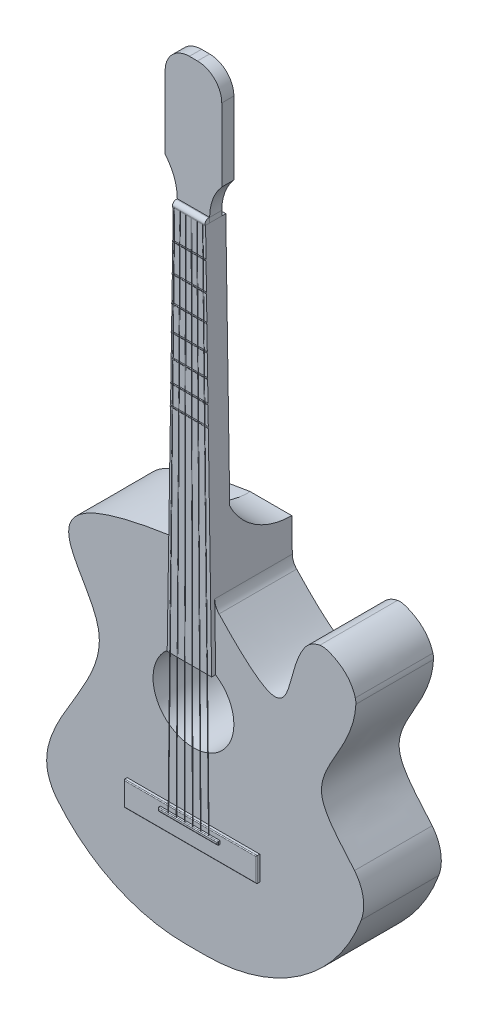
SolidWorks part; units mm, degrees
ref_plane "Front Plane" through (0, 0, 0) normal (0, 0, 1) x (1, 0, 0)
ref_plane "Top Plane" through (0, 0, 0) normal (0, 1, 0) x (1, 0, 0)
ref_plane "Right Plane" through (0, 0, 0) normal (1, 0, 0) x (0, 0, -1)
sketch "Sketch1" plane through (0, 0, 0) normal (0, 0, 1) x (1, 0, 0)
  line L0 (0, 0) -> (40, 0)
  line L2 (0, -480) -> (40, -480)
  line L4 (20, -480) -> (-7.5, -480)
  line L5 (0, 0) -> (-7.5, -480)
  line L7 (40, 0) -> (47.5, -480)
  line L8 (40, -480) -> (47.5, -480)
  dimension "D1" = 40
  dimension "D2" = 480
  dimension "D3" = 27.5
extrude "Boss-Extrude1" add sketch "Sketch1" against normal blind 20 contours L2 L8 L7 L0 L5 L4
sketch "Sketch2" plane through (0, 0, 0) normal (0, 0, 1) x (1, 0, 0)
  line L2 (-7.5, -480) -> (-5.2648, -358.4843)
  line L3 (47.5, -480) -> (-7.5, -480)
  line L4 (10.2196, -786.9686) -> (35.1477, -786.9686)
  line L8 (-5.2648, -358.4843) -> (45.6013, -358.4843)
  line L9 (275.2698, -356.9686) -> (275.2698, -421.9686)
  line L11 (47.5, -480) -> (46.5933, -421.9686)
  line L14 (45.6013, -358.4843) -> (46.3625, -407.203)
  arc A1 (10.2196, -786.9686) -> (-148.7175, -711.4444) centre (10.2196, -581.9686) cw
  arc A2 (35.1477, -786.9686) -> (227.4372, -653.0301) centre (35.1477, -581.9686) ccw
  arc A4 (157.4382, -396.211) -> (176.367, -383.9954) centre (181.9795, -413.4658) cw
  arc A5 (220.8514, -425.0649) -> (220.1344, -418.6037) centre (200.8792, -424.0107) ccw
  arc A6 (227.4372, -653.0301) -> (219.1936, -603.9853) centre (180.5374, -635.698) ccw
  spline S0 degree 2 poles (45.6013, -358.4843) (46.0973, -390.2265) (46.5933, -421.9686) knots 0.023318 0.023318 0.023318 1 1 1
  spline S1 degree 3 poles (-5.2648, -358.4843) (-217.8246, -389.3439) (15.0576, -504.241) (-198.228, -649.3722) (-148.7175, -711.4444) knots 0 0 0 0 0.481381 1 1 1 1
  spline S2 degree 3 poles (219.1936, -603.9853) (202.3906, -583.5033) (147.1519, -529.6114) (218.1524, -476.2006) (220.8514, -425.0649) knots 0.199231 0.199231 0.199231 0.199231 0.323151 0.537685 0.537685 0.537685 0.537685
  spline S3 degree 3 poles (176.367, -383.9954) (180.6636, -383.1772) (200.0573, -388.9291) (215.47, -401.9931) (220.1344, -418.6037) knots 0.180917 0.180917 0.180917 0.180917 0.355528 0.960011 0.960011 0.960011 0.960011
  spline S4 degree 3 poles (157.4382, -396.211) (126.9257, -439.6088) (154.8161, -524.8629) (46.3625, -407.203) knots 0.793266 0.793266 0.793266 0.793266 1 1 1 1
  dimension "D1" = 65
  dimension "D4" = 205
  dimension "D5" = 205
  dimension "D2" = 30
  dimension "D6" = 20
  dimension "D7" = 50
extrude "Boss-Extrude2" add sketch "Sketch2" against normal blind 96 contours A4 S4 S0 L11 L3 L2 S1 A1 L4 A2 A6 S2 A5 S3
fillet "Fillet3" radius 20 1 edges at (46.3625, -407.203, -48)
sketch "Sketch3" plane through (0, 0, 0) normal (0, 0, 1) x (1, 0, 0)
  line L0 (0, 0) -> (40, 0)
sketch "Sketch4" plane through (0, 0, 0) normal (0, 0, 1) x (1, 0, 0)
  line L0 (-7.5, -480) -> (0, 0)
  line L1 (0, 0) -> (40, 0)
  line L2 (40, 0) -> (47.5, -480)
  line L3 (47.5, -480) -> (-7.5, -480)
extrude "Boss-Extrude3" add sketch "Sketch4" along normal blind 5
sketch "Sketch5" plane through (0, 0, 0) normal (0, 0, 1) x (1, 0, 0)
  line L0 (45.6013, -358.4843) -> (-5.2648, -358.4843)
  line L2 (0, 0) -> (-5.6021, -358.5333) construction
  line L3 (-4.8537, -310.6349) -> (44.8537, -310.6349)
  line L4 (40, 0) -> (45.6013, -358.4843) construction
  line L5 (44.8537, -310.6349) -> (45.6013, -358.4843)
  line L6 (-4.8537, -310.6349) -> (-5.6021, -358.5333)
  line L7 (-5.6021, -358.5333) -> (-5.2648, -358.4843)
extrude "Boss-Extrude4" add sketch "Sketch5" against normal blind 96
chamfer "Chamfer1" distance 48 angle 45 1 edges at (20, -310.6349, -96)
sketch "Sketch7" plane through (0, 0, 0) normal (1, 0, 0) x (0, 0, -1)
  line L0 (20, -291.734) -> (20, -310.6349)
  line L1 (20, 0) -> (20, -310.6349) construction
  line L2 (20, -291.734) -> (20, -310.6349)
  line L3 (20, -291.734) -> (20, -310.6349)
  line L4 (96, -379.0809) -> (96, -358.6349)
  line L5 (96, -358.6349) -> (96, -399.527) construction
  line L6 (20, -310.6349) -> (96, -310.6349)
  line L7 (96, -310.6349) -> (96, -358.6349)
  arc A0 (96, -358.6349) -> (20, -310.6349) centre (96, -274.4682) cw
extrude "Cut-Extrude1" cut sketch "Sketch7" along normal mid plane 110 contours A0 L7 L6
sketch "Sketch8" plane through (0, 0, 0) normal (0, 0, 1) x (1, 0, 0)
  line L0 (20, -480) -> (20, -472)
  line L1 (-7.5, -480) -> (47.5, -480) construction
  line L2 (20, -472) -> (20, -572)
  circle A0 centre (20, -522) radius 50
  dimension "D1" = 8
  dimension "D2" = 100
sketch "Sketch9" plane through (0, 0, 0) normal (0, 0, 1) x (1, 0, 0)
  circle A0 centre (20, -522) radius 50
sketch "Sketch28" plane through (0, 0, 0) normal (0, 0, 1) x (1, 0, 0)
  circle A0 centre (20, -522) radius 50
extrude "Cut-Extrude14" cut sketch "Sketch28" against normal blind 80
sketch "Sketch30" plane through (0, 0, 5) normal (0, 0, 1) x (1, 0, 0)
  line L0 (0, -162) -> (-2.5312, -162)
  line L3 (0, -162) -> (40.5938, -162)
  line L8 (39.7524, -36) -> (40.5625, -36)
  line L9 (0, -36) -> (39.7524, -36)
  line L11 (0, -38) -> (39.7524, -38)
  line L13 (47.5, -480) -> (40, 0) construction
  line L14 (40.5625, -36) -> (40.5938, -38)
  line L15 (40.5938, -38) -> (39.7524, -38)
  line L16 (0, -36) -> (-0.5625, -36)
  line L17 (0, 0) -> (-7.5, -480) construction
  line L18 (-0.5625, -36) -> (-0.5937, -38)
  line L19 (-0.5937, -38) -> (0, -38)
  line L20 (0, -71) -> (-1.1094, -71)
  line L21 (0, -71) -> (39.7524, -71)
  line L23 (0, -73) -> (39.7524, -73)
  line L25 (-1.1094, -71) -> (-1.1406, -73)
  line L26 (-1.1406, -73) -> (0, -73)
  line L27 (39.7524, -71) -> (41.1094, -71)
  line L28 (41.1094, -71) -> (41.1406, -73)
  line L29 (41.1406, -73) -> (39.7524, -73)
  line L30 (39.7524, -103) -> (41.6094, -103)
  line L31 (0, -103) -> (39.7524, -103)
  line L33 (0, -105) -> (39.7524, -105)
  line L35 (41.6094, -103) -> (41.6406, -105)
  line L36 (41.6406, -105) -> (39.7524, -105)
  line L37 (0, -103) -> (-1.6094, -103)
  line L38 (-1.6094, -103) -> (-1.6406, -105)
  line L39 (-1.6406, -105) -> (0, -105)
  line L40 (0, -134) -> (-2.0937, -134)
  line L41 (0, -134) -> (40.5938, -134)
  line L43 (0, -136) -> (40.5938, -136)
  line L45 (-2.0937, -134) -> (-2.125, -136)
  line L46 (-2.125, -136) -> (0, -136)
  line L47 (40.5938, -134) -> (42.0938, -134)
  line L48 (42.0938, -134) -> (42.125, -136)
  line L49 (42.125, -136) -> (40.5938, -136)
  line L50 (0, -164) -> (40.5938, -164)
  line L52 (-2.5312, -162) -> (-2.5625, -164)
  line L53 (-2.5625, -164) -> (0, -164)
  line L54 (40.5938, -162) -> (42.5313, -162)
  line L55 (42.5313, -162) -> (42.5625, -164)
  line L56 (42.5625, -164) -> (40.5938, -164)
  line L57 (0, -189) -> (-2.9531, -189)
  line L58 (0, -189) -> (39.7524, -189)
  line L60 (0, -191) -> (39.7524, -191)
  line L62 (-2.9531, -189) -> (-2.9844, -191)
  line L63 (-2.9844, -191) -> (0, -191)
  line L64 (39.7524, -189) -> (42.9531, -189)
  line L65 (42.9531, -189) -> (42.9844, -191)
  line L66 (42.9844, -191) -> (39.7524, -191)
  line L67 (0, -214) -> (-3.3437, -214)
  line L68 (0, -214) -> (40.5938, -214)
  line L70 (0, -216) -> (40.5938, -216)
  line L72 (-3.3437, -214) -> (-3.375, -216)
  line L73 (-3.375, -216) -> (0, -216)
  line L74 (40.5938, -214) -> (43.3438, -214)
  line L75 (43.3438, -214) -> (43.375, -216)
  line L76 (43.375, -216) -> (40.5938, -216)
  dimension "D2" = 35
  dimension "D3" = 32
  dimension "D4" = 31
  dimension "D5" = 28
  dimension "D6" = 27
  dimension "D7" = 25
  dimension "D8" = 2
  dimension "D9" = 2
  dimension "D10" = 2
  dimension "D11" = 2
  dimension "D12" = 2
  dimension "D13" = 2
  dimension "D14" = 2
extrude "Boss-Extrude18" add sketch "Sketch30" along normal blind 0.5
fillet "Fillet31" radius 1 14 edges at (20, -216, 5.5) (20, -214, 5.5) (20, -191, 5.5) (20, -189, 5.5) (20, -164, 5.5) (20, -162, 5.5) (20, -136, 5.5) (20, -134, 5.5) (20, -105, 5.5) (20, -103, 5.5) (20, -73, 5.5) (20, -71, 5.5) (20, -38, 5.5) (20, -36, 5.5)
sketch "Sketch31" plane through (0, 0, 0) normal (0, 0, 1) x (1, 0, 0)
  line L0 (0, 0) -> (0, 6)
  line L1 (40, 0) -> (40, 6)
  line L2 (40, 6) -> (0, 6)
  line L3 (0, 0) -> (40, 0)
  dimension "D1" = 6
sketch "Sketch32" plane through (0, 0, 5) normal (0, 0, 1) x (1, 0, 0)
  line L1 (0, 0) -> (40, 0)
  line L2 (0, 0) -> (0, 6)
  line L3 (0, 6) -> (40, 6)
  line L4 (40, 0) -> (40, 6)
extrude "Boss-Extrude19" add sketch "Sketch32" along normal blind 1 separate body
sketch "Sketch33" plane through (0, 0, 5) normal (0, 0, -1) x (-1, 0, 0)
  line L1 (-40, 0) -> (0, 0)
  line L2 (-40, 0) -> (-40, 6)
  line L3 (-40, 6) -> (0, 6)
  line L4 (0, 0) -> (0, 6)
extrude "Boss-Extrude20" add sketch "Sketch33" along normal blind 5
fillet "Fillet32" radius 5 1 edges at (20, 6, 6)
sketch "Sketch34" plane through (0, 0, 0) normal (0, 0, 1) x (1, 0, 0)
  line L1 (20, -645) -> (-17, -645)
  line L2 (20, -645) -> (-62, -645)
  line L3 (20, -645) -> (102, -645)
  line L4 (-62, -645) -> (-62, -675)
  line L5 (-62, -675) -> (102, -675)
  line L6 (102, -675) -> (102, -645)
  line L8 (20, -651) -> (-17, -651)
  line L9 (-17, -651) -> (-17, -655)
  line L10 (-17, -655) -> (57, -655)
  line L11 (57, -655) -> (57, -651)
  line L12 (57, -651) -> (20, -651)
  dimension "D2" = 37
  dimension "D3" = 82
  dimension "D4" = 82
  dimension "D5" = 30
  dimension "D6" = 6
  dimension "D7" = 4
  dimension "D8" = 74
extrude "Boss-Extrude21" add sketch "Sketch34" along normal blind 4 contours L5 L6 L3 L1 L2 L4 L12 L11 L10 L9 L8
sketch "Sketch35" plane through (0, 0, 4) normal (0, 0, 1) x (1, 0, 0)
  line L1 (-17, -655) -> (57, -655)
  line L2 (-17, -655) -> (-17, -651)
  line L3 (-17, -651) -> (57, -651)
  line L4 (57, -655) -> (57, -651)
extrude "Boss-Extrude22" add sketch "Sketch35" along normal blind 3 separate body
fillet "Fillet33" radius 1 4 edges at (102, -660, 4) (20, -675, 4) (-62, -660, 4) (20, -645, 4)
fillet "Fillet34" radius 1 4 edges at (-17, -653, 7) (57, -653, 7) (20, -655, 7) (20, -651, 7)
sketch "Sketch36" plane through (0, 0, 6) normal (0, 0, 1) x (1, 0, 0)
  line L0 (0, 0) -> (2.5, 0)
  line L1 (0, 0) -> (40, 0) construction
  line L2 (2.5, 0) -> (9.5, 0)
  line L3 (9.5, 0) -> (16.5, 0)
  line L4 (16.5, 0) -> (23.5, 0)
  line L5 (23.5, 0) -> (30.5, 0)
  line L6 (30.5, 0) -> (37.5, 0)
  line L7 (-16, -653) -> (-5, -653)
  line L8 (-16, -652) -> (-16, -654) construction
  line L9 (-5, -653) -> (5, -653)
  line L10 (5, -653) -> (15, -653)
  line L11 (15, -653) -> (25, -653)
  line L12 (25, -653) -> (35, -653)
  line L13 (35, -653) -> (45, -653)
  dimension "D1" = 2.5
  dimension "D2" = 7
  dimension "D3" = 7
  dimension "D4" = 7
  dimension "D5" = 7
  dimension "D6" = 7
  dimension "D7" = 11
  dimension "D8" = 10
  dimension "D9" = 10
  dimension "D10" = 10
  dimension "D11" = 10
  dimension "D12" = 10
sketch "Sketch44" plane through (0, 0, 0) normal (0, 0, -1) x (-1, 0, 0)
  line L0 (-40, 0) -> (0, 0)
  line L1 (0, 0) -> (0, 6)
  line L2 (0, 6) -> (-40, 6)
  line L3 (-40, 6) -> (-40, 0)
  line L4 (-20, 6) -> (-40, 6)
  line L5 (-20, 6) -> (0, 6)
  line L7 (-55, 46) -> (-55, 136)
  line L8 (-25, 166) -> (-15, 166)
  line L9 (15, 136) -> (15, 46)
  arc A0 (-40, 6) -> (-55, 46) centre (-100.8333, 6) ccw
  arc A1 (0, 6) -> (15, 46) centre (60.8333, 6) cw
  arc A2 (-15, 166) -> (15, 136) centre (-15, 136) cw
  arc A3 (-55, 136) -> (-25, 166) centre (-25, 136) cw
  point P17 (15, 166)
  point P20 (-55, 166)
  line M15 (0, 6) -> (-40, 6)
  dimension "D1" = 30
  dimension "D4" = 120
  dimension "D5" = 70
extrude "Boss-Extrude23" add sketch "Sketch44" along normal blind 15 separate body contours A3 L7 A0 L2 A1 L9 A2 L8 M15
sketch "Sketch45" plane through (0, 0, -15) normal (0, 0, -1) x (-1, 0, 0)
  line L0 (-55, 46) -> (-55, 136)
  line L1 (15, 46) -> (15, 136)
  line L2 (-40, 6) -> (-40, 0)
  line L3 (-40, 0) -> (0, 0)
  line L4 (0, 0) -> (0, 6)
  arc A0 (-40, 6) -> (-55, 46) centre (-100.8333, 6) ccw
  arc A1 (0, 6) -> (15, 46) centre (60.8333, 6) cw
ref_plane "Plane1" through (0, 0, 6) normal (0, 0, -1) x (-1, 0, 0)
sketch "Sketch46" plane through (0, 0, 6) normal (0, 0, -1) x (-1, 0, 0)
  line L0 (-45, -653) -> (-37.5, 0)
  line L1 (-35, -653) -> (-30.5, 0)
  line L2 (-25, -653) -> (-23.5, 0)
  line L3 (-15, -653) -> (-16.5, 0)
  line L4 (-5, -653) -> (-9.5, 0)
  line L5 (5, -653) -> (-2.5, 0)
sweep "Sweep9" add path "Sketch46" circular profile diameter 0.5 parameters "D3"=0.5
sketch "Sketch110" plane through (0, 0, 6) normal (0, 0, -1) x (-1, 0, 0)
  line L0 (-5, -653) -> (-9.5, 0)
sweep "Sweep14" add path "Sketch110" circular profile diameter 0.5 parameters "D3"=0.5
sketch "Sketch125" plane through (0, 0, 6) normal (0, 0, -1) x (-1, 0, 0)
  line L0 (-15, -653) -> (-16.5, 0)
sweep "Sweep15" add path "Sketch125" circular profile diameter 0.5 parameters "D3"=0.5
sketch "Sketch132" plane through (0, 0, 6) normal (0, 0, -1) x (-1, 0, 0)
  line L0 (-25, -653) -> (-23.5, 0)
sweep "Sweep16" add path "Sketch132" circular profile diameter 0.5 parameters "D3"=0.5
sketch "Sketch139" plane through (0, 0, 6) normal (0, 0, -1) x (-1, 0, 0)
  line L0 (-35, -653) -> (-30.5, 0)
sweep "Sweep17" add path "Sketch139" circular profile diameter 0.5 parameters "D3"=0.5
sketch "Sketch146" plane through (0, 0, 6) normal (0, 0, -1) x (-1, 0, 0)
  line L0 (-45, -653) -> (-37.5, 0)
sweep "Sweep18" add path "Sketch146" circular profile diameter 0.5 parameters "D3"=0.5
